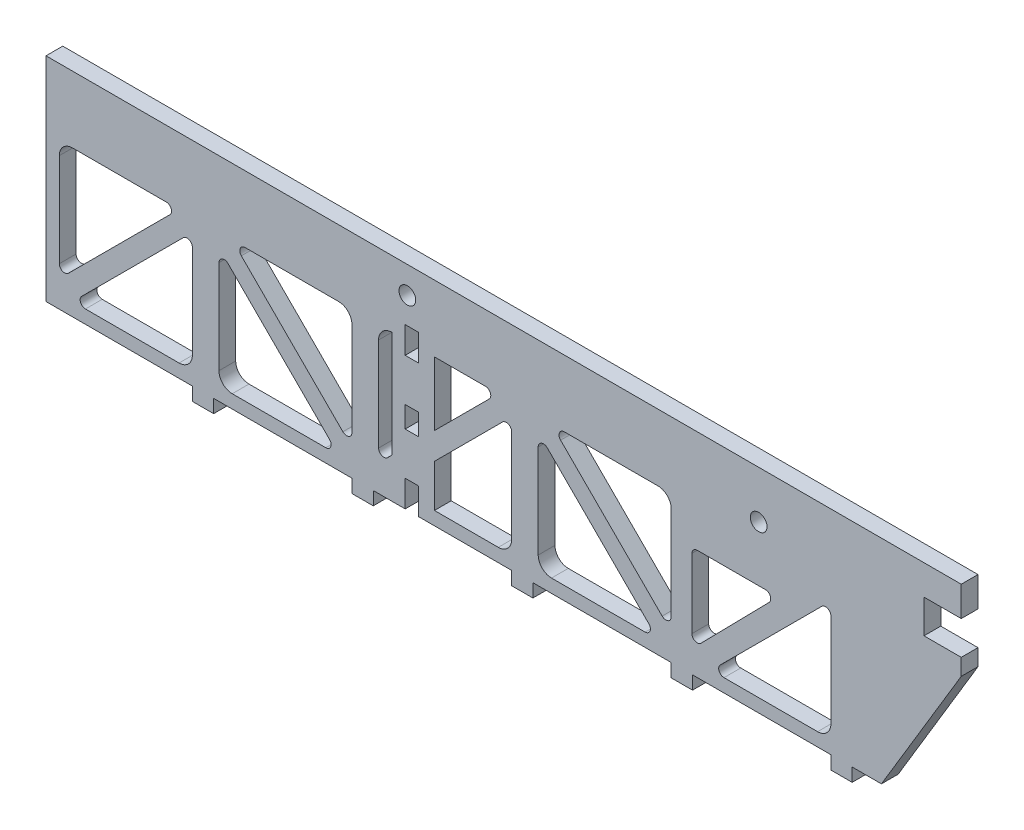
SolidWorks part; units mm, degrees
material "Pine"
ref_plane "Front Plane" through (0, 0, 0) normal (0, 0, 1) x (1, 0, 0)
ref_plane "Top Plane" through (0, 0, 0) normal (0, 1, 0) x (1, 0, 0)
ref_plane "Right Plane" through (0, 0, 0) normal (1, 0, 0) x (0, 0, -1)
sketch "Model" plane through (0, 0, 0) normal (0, 0, 1) x (1, 0, 0)
  line L0 (312.6855, 15.1239) -> (345.2281, 48.2988)
  line L1 (343.4149, 52.6175) -> (310.8722, 52.6175)
  line L2 (308.3322, 50.0775) -> (308.3322, 16.9026)
  line L8 (171.2321, 6.35) -> (215.9, 6.35)
  line L9 (217.9139, 59.1639) -> (169.4361, 10.6861)
  line L10 (222.25, 57.3679) -> (222.25, 12.7)
  line L11 (234.95, 57.3679) -> (234.95, 12.7)
  line L12 (239.2861, 59.1639) -> (287.7639, 10.6861)
  line L13 (241.3, 6.35) -> (285.9679, 6.35)
  line L14 (294.1139, 17.0361) -> (245.6361, 65.5139)
  line L15 (247.4321, 69.85) -> (292.1, 69.85)
  line L16 (298.45, 63.5) -> (298.45, 18.8321)
  line L17 (323.6321, 6.35) -> (368.3, 6.35)
  line L18 (370.3139, 59.1639) -> (321.8361, 10.6861)
  line L19 (374.65, 57.3679) -> (374.65, 12.7)
  line L20 (18.8321, 6.35) -> (63.5, 6.35)
  line L21 (17.0361, 10.6861) -> (65.5139, 59.1639)
  line L22 (69.85, 57.3679) -> (69.85, 12.7)
  line L23 (82.55, 57.3679) -> (82.55, 12.7)
  line L24 (86.8861, 59.1639) -> (135.3639, 10.6861)
  line L25 (88.9, 6.35) -> (133.5679, 6.35)
  line L26 (93.2361, 65.5139) -> (141.7139, 17.0361)
  line L27 (95.0321, 69.85) -> (139.7, 69.85)
  line L28 (146.05, 63.5) -> (146.05, 18.8321)
  line L29 (163.0861, 17.0361) -> (211.5639, 65.5139)
  line L30 (158.75, 63.5) -> (158.75, 18.8321)
  line L31 (165.1, 69.85) -> (209.7679, 69.85)
  line L35 (419.1, 87.376) -> (419.1, 71.374)
  line L36 (436.88, 87.376) -> (419.1, 87.376)
  line L37 (436.88, 87.376) -> (436.88, 95.25)
  line L38 (0, 95.25) -> (436.88, 95.25)
  line L39 (0, 0) -> (0, 95.25)
  line L40 (0, 0) -> (398.78, 0)
  line L41 (436.88, 63.5) -> (398.78, 0)
  line L42 (436.88, 63.5) -> (436.88, 71.374)
  line L43 (419.1, 71.374) -> (436.88, 71.374)
  line L44 (6.35, 63.5) -> (6.35, 18.8321)
  line L45 (12.7, 69.85) -> (57.3679, 69.85)
  line L46 (59.1639, 65.5139) -> (10.6861, 17.0361)
  arc A0 (215.9, 6.35) -> (222.25, 12.7) centre (215.9, 12.7) ccw
  arc A1 (169.4361, 10.6861) -> (171.2321, 6.35) centre (171.2321, 8.89) ccw
  arc A2 (222.25, 57.3679) -> (217.9139, 59.1639) centre (219.71, 57.3679) ccw
  arc A3 (239.2861, 59.1639) -> (234.95, 57.3679) centre (237.49, 57.3679) ccw
  arc A4 (285.9679, 6.35) -> (287.7639, 10.6861) centre (285.9679, 8.89) ccw
  arc A5 (234.95, 12.7) -> (241.3, 6.35) centre (241.3, 12.7) ccw
  arc A6 (247.4321, 69.85) -> (245.6361, 65.5139) centre (247.4321, 67.31) ccw
  arc A7 (298.45, 63.5) -> (292.1, 69.85) centre (292.1, 63.5) ccw
  arc A8 (294.1139, 17.0361) -> (298.45, 18.8321) centre (295.91, 18.8321) ccw
  arc A9 (321.8361, 10.6861) -> (323.6321, 6.35) centre (323.6321, 8.89) ccw
  arc A10 (374.65, 57.3679) -> (370.3139, 59.1639) centre (372.11, 57.3679) ccw
  arc A11 (368.3, 6.35) -> (374.65, 12.7) centre (368.3, 12.7) ccw
  arc A12 (63.5, 6.35) -> (69.85, 12.7) centre (63.5, 12.7) ccw
  arc A13 (17.0361, 10.6861) -> (18.8321, 6.35) centre (18.8321, 8.89) ccw
  arc A14 (69.85, 57.3679) -> (65.5139, 59.1639) centre (67.31, 57.3679) ccw
  arc A15 (86.8861, 59.1639) -> (82.55, 57.3679) centre (85.09, 57.3679) ccw
  arc A16 (133.5679, 6.35) -> (135.3639, 10.6861) centre (133.5679, 8.89) ccw
  arc A17 (82.55, 12.7) -> (88.9, 6.35) centre (88.9, 12.7) ccw
  arc A18 (95.0321, 69.85) -> (93.2361, 65.5139) centre (95.0321, 67.31) ccw
  arc A19 (146.05, 63.5) -> (139.7, 69.85) centre (139.7, 63.5) ccw
  arc A20 (141.7139, 17.0361) -> (146.05, 18.8321) centre (143.51, 18.8321) ccw
  arc A21 (158.75, 18.8321) -> (163.0861, 17.0361) centre (161.29, 18.8321) ccw
  arc A22 (165.1, 69.85) -> (158.75, 63.5) centre (165.1, 63.5) ccw
  arc A23 (211.5639, 65.5139) -> (209.7679, 69.85) centre (209.7679, 67.31) ccw
  arc A24 (345.2281, 48.2988) -> (343.4149, 52.6175) centre (343.4149, 50.0775) ccw
  arc A25 (310.8722, 52.6175) -> (308.3322, 50.0775) centre (310.8722, 50.0775) ccw
  arc A26 (312.6855, 15.1239) -> (308.3322, 16.9026) centre (310.8722, 16.9026) cw
  arc A27 (6.35, 18.8321) -> (10.6861, 17.0361) centre (8.89, 18.8321) ccw
  arc A28 (12.7, 69.85) -> (6.35, 63.5) centre (12.7, 63.5) ccw
  arc A29 (59.1639, 65.5139) -> (57.3679, 69.85) centre (57.3679, 67.31) ccw
  circle A30 centre (172.4917, 88.8013) radius 4
  circle A31 centre (340.1736, 78.9553) radius 4
  dimension "D2" = 6.4487
  dimension "D3" = 172.4917
  dimension "D4" = 8
  dimension "D5" = 9.846
  dimension "D6" = 8
  dimension "D8" = 2.54
  dimension "D1" = 95.25
  dimension "D7" = 167.6819
extrude "Boss-Extrude2" add sketch "Model" along normal blind 8
sketch "Sketch1" plane through (0, 0, 8) normal (0, 0, 1) x (1, 0, 0)
  line L0 (69.85, 12.7) -> (69.85, 0) construction
  line L1 (146.05, 95.25) -> (146.05, 0) construction
  line L2 (146.05, 18.8321) -> (146.05, 63.5) construction
  line L3 (0, 0) -> (398.78, 0) construction
  line L4 (222.25, 95.25) -> (222.25, 0) construction
  line L5 (222.25, 12.7) -> (222.25, 57.3679) construction
  line L6 (298.45, 18.8321) -> (298.45, 0) construction
  line L7 (146.05, 0) -> (156.21, 0)
  line L8 (69.85, 0) -> (80.01, 0)
  line L9 (69.85, 0) -> (69.85, -6.35)
  line L10 (69.85, -6.35) -> (80.01, -6.35)
  line L11 (80.01, 0) -> (80.01, -6.35)
  line L16 (222.25, 0) -> (232.41, 0)
  line L17 (222.25, 0) -> (222.25, -6.35)
  line L18 (222.25, -6.35) -> (232.41, -6.35)
  line L19 (232.41, 0) -> (232.41, -6.35)
  line L20 (146.05, 0) -> (146.05, -6.35)
  line L21 (146.05, -6.35) -> (156.21, -6.35)
  line L22 (156.21, 0) -> (156.21, -6.35)
  line L24 (374.65, 12.7) -> (374.65, 0) construction
  line L25 (374.65, 12.7) -> (374.65, 57.3679) construction
  line L27 (298.45, 0) -> (308.61, 0)
  line L28 (298.45, 0) -> (298.45, -6.35)
  line L29 (298.45, -6.35) -> (308.61, -6.35)
  line L30 (308.61, 0) -> (308.61, -6.35)
  line L31 (374.65, 0) -> (384.81, 0)
  line L32 (374.65, 0) -> (374.65, -6.35)
  line L33 (374.65, -6.35) -> (384.81, -6.35)
  line L34 (384.81, 0) -> (384.81, -6.35)
  line L39 (0, 101.6) -> (436.88, 101.6)
  line L53 (0, 95.25) -> (0, 101.6)
  line L55 (436.88, 95.25) -> (436.88, 101.6)
  line L56 (436.88, 95.25) -> (0, 95.25) construction
  line L57 (0, 95.25) -> (436.88, 95.25)
  arc A0 (368.3, 6.35) -> (374.65, 12.7) centre (368.3, 12.7) ccw construction
  dimension "D1" = 10.16
  dimension "D2" = 6.35
  dimension "D3" = 10.16
  dimension "D4" = 6.35
  dimension "D5" = 10.16
  dimension "D6" = 10.16
  dimension "D7" = 10.16
  dimension "D13" = 6.35
extrude "Boss-Extrude3" add sketch "Sketch1" against normal up to surface (8 mm away) up to face at (321.5295, 39.2174, 0)
sketch "Sketch2" plane through (0, 0, 8) normal (0, 0, 1) x (1, 0, 0)
  line L0 (156.21, 0) -> (222.25, 0) construction
  line L1 (165.1, 79.7539) -> (185.42, 79.7539)
  line L2 (165.1, 79.7539) -> (165.1, 0)
  line L3 (165.1, 0) -> (185.42, 0)
  line L4 (185.42, 79.7539) -> (185.42, 0)
  line L5 (158.75, 63.5) -> (158.75, 18.8321) construction
  line L7 (171.45, 0) -> (177.8, 0)
  line L8 (171.45, 0) -> (171.45, 12.7)
  line L9 (171.45, 12.7) -> (177.8, 12.7)
  line L10 (177.8, 0) -> (177.8, 12.7)
  line L11 (171.45, 33.02) -> (177.8, 33.02)
  line L12 (171.45, 33.02) -> (171.45, 43.18)
  line L13 (171.45, 43.18) -> (177.8, 43.18)
  line L14 (177.8, 33.02) -> (177.8, 43.18)
  line L15 (171.45, 63.5) -> (177.8, 63.5)
  line L16 (171.45, 63.5) -> (171.45, 76.2)
  line L17 (171.45, 76.2) -> (177.8, 76.2)
  line L18 (177.8, 63.5) -> (177.8, 76.2)
  line L19 (146.05, -6.35) -> (156.21, -6.35) construction
  dimension "D1" = 6.35
  dimension "D2" = 20.32
  dimension "D3" = 6.35
  dimension "D4" = 6.35
  dimension "D5" = 6.35
  dimension "D6" = 12.7
  dimension "D7" = 20.32
  dimension "D8" = 20.32
  dimension "D9" = 10.16
  dimension "D10" = 12.7
extrude "Boss-Extrude4" add sketch "Sketch2" against normal up to surface (8 mm away) contours L10 L3 L4 L1 L2 L8 L9 L18 L15 L16 L17 L14 L11 L12 L13 region at (175.26, 78.9309, 8) up to face at (321.5295, 39.2174, 0)
extrude "Cut-Extrude1" cut sketch "Sketch2<3>" along direction (0, 0, 1) on the side against the normal up to surface (8 mm away) from surface contours L3 L10 L9 L8 | L15 L18 L17 L16 region at (174.625, 6.35, 8) region at (174.625, 69.85, 8) up to face at (174.625, 9.525, 0) starting at face at (174.625, 9.525, 8)
sketch "Sketch2<3>" plane through (0, 0, 8) normal (0, 0, 1) x (1, 0, 0) same geometry as "Sketch2"
